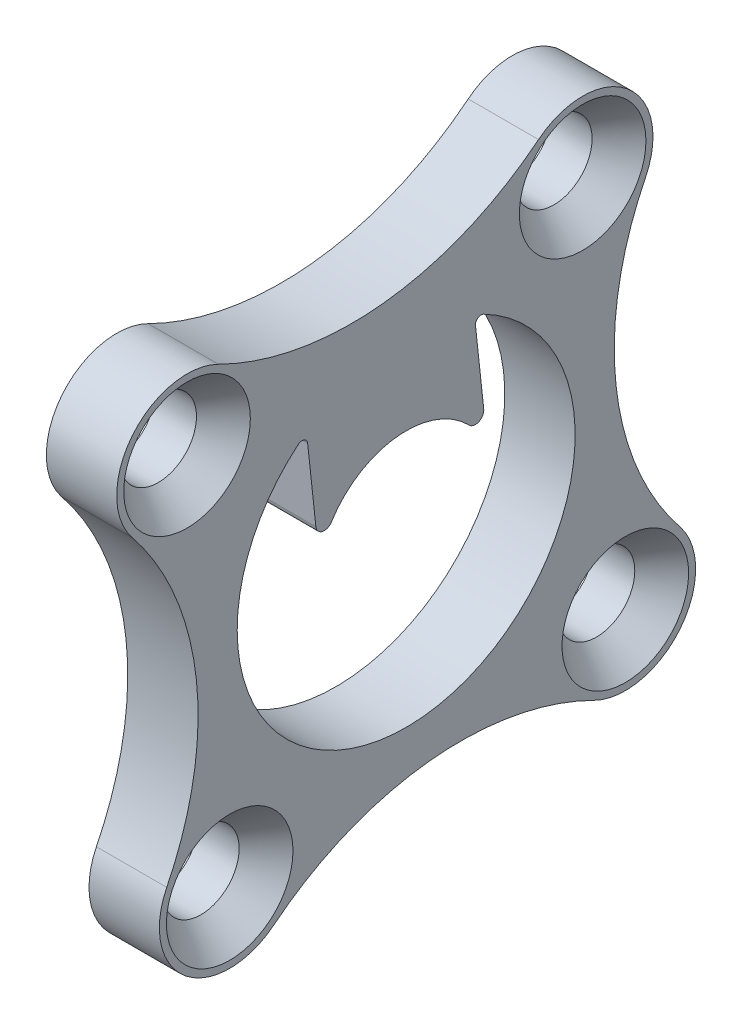
SolidWorks part; units mm, degrees
material "6061-T6 (SS)"
ref_plane "Front Plane" through (0, 0, 0) normal (0, 0, 1) x (1, 0, 0)
ref_plane "Top Plane" through (0, 0, 0) normal (0, 1, 0) x (1, 0, 0)
ref_plane "Right Plane" through (0, 0, 0) normal (1, 0, 0) x (0, 0, -1)
sketch "Sketch1" plane through (-42.315, 0, 0) normal (-1, 0, 0) x (0, 0, 1)
  line L0 (4.4478, 5.7077) -> (4.0751, 2.2522)
  line L1 (4.6292, 7.3892) -> (4.4314, 5.5558) construction
  line L2 (-3.501, 3.0694) -> (-3.1282, 6.525)
  line L3 (-2.9468, 8.2065) -> (-3.4815, 3.2497) construction
  line L5 (4.4314, 5.5558) -> (3.9072, 0.6962) construction
  line L6 (7.9653, -9.8916) -> (-7.9653, 9.8916) construction
  line L7 (-9.8916, -7.9653) -> (9.8916, 7.9653) construction
  arc A0 (4.0751, 2.2522) -> (3.3725, 2.0922) centre (3.6963, 2.293) cw
  arc A1 (3.3725, 2.0922) -> (-2.8487, 2.7633) centre (0, 0) ccw
  arc A2 (-2.8487, 2.7633) -> (-3.501, 3.0694) centre (-3.1222, 3.0286) cw
  circle A3 centre (0, 0) radius 3.9687 construction
  circle A4 centre (0, 0) radius 3.9687 construction
  arc A5 (4.4478, 5.7077) -> (4.8623, 5.8762) centre (4.7004, 5.6805) cw
  arc A8 (4.8623, 5.8762) -> (-3.4972, 6.778) centre (0, 0) cw
  arc A9 (-3.4972, 6.778) -> (-3.1282, 6.525) centre (-3.3807, 6.5522) cw
  circle A10 centre (0, 0) radius 15.875
  arc A11 (-3.5162, 6.6247) -> (4.8482, 5.7223) centre (0, 0) ccw construction
  circle A12 centre (9.8916, 7.9653) radius 3.175 construction
  circle A13 centre (9.8916, 7.9653) radius 2.6924 construction
  circle A14 centre (0, 0) radius 9.525 construction
  dimension "D1" = 0.381
  dimension "D2" = 0.254
  dimension "D3" = 25.4
  dimension "D4" = 0.127
  dimension "D6" = 5.3848
  dimension "D7" = 19.05
  dimension "D5" = 45
extrude "Boss-Extrude1" add sketch "Sketch1" against normal blind 3.175
sketch "Sketch2" plane through (-42.315, 0, 0) normal (-1, 0, 0) x (0, 0, 1)
  line L0 (-9.8916, -7.9653) -> (9.8916, 7.9653) construction
  line L1 (4.4478, 5.7077) -> (4.0751, 2.2522) construction
  line L2 (9.4701, -1.0216) -> (15.7834, -1.7027)
  arc A0 (12.3645, 9.9566) -> (15.7834, -1.7027) centre (0, 0) cw
  circle A1 centre (0, 0) radius 15.875 construction
  circle A3 centre (0, 0) radius 9.525 construction
  arc A5 (12.3658, 5.9755) -> (12.3645, 9.9566) centre (9.8916, 7.9653) ccw
  circle A6 centre (9.8916, 7.9653) radius 3.175 construction
  arc A7 (12.3658, 5.9755) -> (9.4701, -1.0216) centre (22.8627, -2.4664) ccw
extrude "Cut-Extrude1" cut sketch "Sketch2" against normal through all
mirror "Mirror1" about plane through (-39.14, -1.0216, 9.4701) normal (0, -0.9942, -0.1073) of "Cut-Extrude1"
pattern_circular "CirPattern2" count 4 over 360 about axis through (-42.315, 0, 0) along (-1, 0, 0) of "Cut-Extrude1", "Mirror1"
hole_wizard "CSK for #4 Flat Head Machine Screw1" positions "Sketch3" profile "Sketch4" countersink size "#4" standard "ANSI Inch" end condition up to next
sketch "Sketch3" plane through (-39.14, 0, 0) normal (1, 0, 0) x (0, 0, -1)
  point P0 (7.9653, 9.8916)
  point P3 (7.9653, 9.8916)
  point P6 (7.9653, 9.8916)
  point P9 (7.9653, 9.8916)
  point P13 (-9.8916, 7.9653)
  point P16 (-7.9653, -9.8916)
  point P19 (9.8916, -7.9653)
sketch "Sketch4" plane through (-39.14, 9.8916, -7.9653) normal (0, 1, 0) x (0, 0, -1)
  line L0 (0, 0) -> (0, 3.175)
  line L1 (0, 3.175) -> (1.7272, 3.175)
  line L2 (1.7272, 3.175) -> (1.7272, 1.3003)
  line L3 (1.7272, 1.3003) -> (2.8575, 0)
  line L5 (2.8575, 0) -> (0, 0)
  line L6 (-1.7272, 1.3003) -> (-2.8575, 0) construction
  line L11 (0, -6.35) -> (0, 107.95) construction
  dimension "Thru Hole Dia." = 3.4544
  dimension "Thru Hole Depth" = 3.175
  dimension "Near C'Sink Dia." = 5.715
  dimension "Near C'Sink Angle" = 82
